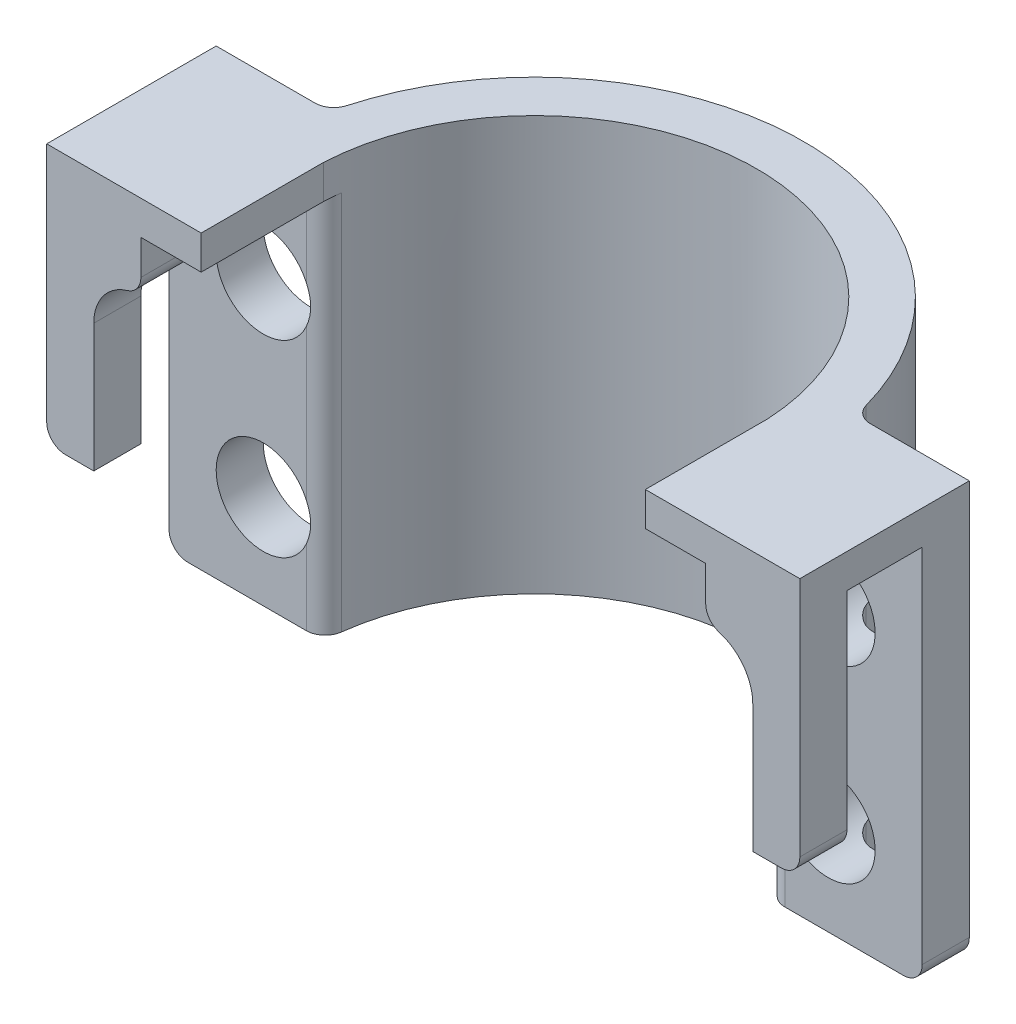
SolidWorks part; units mm, degrees
note: '?' marks a value the reader was unsure of.
ref_plane "Front Plane" through (0, 0, 0) normal (0, 0, 1) x (1, 0, 0)
ref_plane "Top Plane" through (0, 0, 0) normal (0, 1, 0) x (1, 0, 0)
ref_plane "Right Plane" through (0, 0, 0) normal (1, 0, 0) x (0, 0, -1)
sketch "Sketch2" plane through (0, 0, 0) normal (0, 1, 0) x (1, 0, 0)
  line L0 (0, 0) -> (-10.4194, 0)
  line L1 (-10.4194, 0) -> (-10.4194, 3.175)
  line L2 (-10.4194, 3.175) -> (-2.7628, 3.175)
  line L3 (32.7241, 3.175) -> (40.3806, 3.175)
  line L4 (40.3806, 3.175) -> (40.3806, 0)
  line L5 (40.3806, 0) -> (29.9613, 0)
  line L6 (14.9806, 0.1727) -> (14.9806, 50000.1727) construction
  circle A0 centre (14.9806, -0.762) radius 15 construction
  arc A1 (29.9613, 0) -> (0, 0) centre (14.9806, -0.762) ccw
  arc A2 (32.7241, 3.175) -> (-2.7628, 3.175) centre (14.9806, -0.762) ccw
  point P5 (-4.0694, 0)
  point P8 (34.0306, 0)
  dimension "D1" = 15
  dimension "D2" = 3.175
  dimension "D3" = 38.1
  dimension "D4" = 3.175
  dimension "D5" = 6.35
  dimension "D6" = 0.762
extrude "Boss-Extrude1" add sketch "Sketch2" against normal blind 27.94
sketch "Sketch3" plane through (0, 0, 0) normal (0, 0, 1) x (1, 0, 0)
  line L0 (14.9806, 0) -> (14.9806, -50000) construction
  line L1 (29.9613, 0) -> (0, 0) construction
  line L2 (-10.4194, 0) -> (0, 0) construction
  circle A0 centre (-4.0694, -8.89) radius 3.175
  circle A1 centre (34.0306, -8.89) radius 3.175
  circle A2 centre (-4.0694, -21.59) radius 3.175
  circle A3 centre (34.0306, -21.59) radius 3.175
  point P8 (14.9806, 0)
  dimension "D1" = 6.35
  dimension "D4" = 12.7
  dimension "D2" = 38.1
  dimension "D3" = 8.89
extrude "Cut-Extrude1" cut sketch "Sketch3" against normal through all
sketch "Sketch4" plane through (40.3806, 0, 0) normal (1, 0, 0) x (0, 0, -1)
  line L0 (-5.08, -17.526) -> (-8.255, -17.526)
  line L1 (-8.255, -17.526) -> (-8.255, 0)
  line L2 (-8.255, 0) -> (0, 0)
  line L3 (0, 0) -> (0, -2.286)
  line L4 (0, -27.94) -> (0, 0) construction
  line L5 (0, -2.286) -> (-5.08, -2.286)
  line L6 (-5.08, -2.286) -> (-5.08, -17.526)
  dimension "D1" = 2.286
  dimension "D2" = 3.175
  dimension "D3" = 5.08
  dimension "D4" = 15.24
extrude "Boss-Extrude2" add sketch "Sketch4" against normal up to vertex (10.7129 mm away)
sketch "Sketch5" plane through (0, 0, 8.255) normal (0, 0, 1) x (1, 0, 0)
  line L0 (29.9613, -17.526) -> (40.3806, -17.526) construction
  line L4 (37.2056, -8.89) -> (37.2056, -17.526)
  line L5 (29.9613, -2.286) -> (34.0306, -2.286)
  line L6 (29.9613, 0) -> (29.9613, -17.526) construction
  line L7 (34.0306, -2.286) -> (34.0306, -5.715)
  line L8 (29.9613, -2.286) -> (29.9613, -17.526)
  line L9 (29.9613, -27.94) -> (29.9613, -2.286) construction
  line L10 (29.9613, -17.526) -> (37.2056, -17.526)
  line L11 (29.9613, -2.286) -> (40.3806, -2.286) construction
  arc A2 (37.2056, -8.89) -> (34.0306, -5.715) centre (34.0306, -8.89) ccw
  circle A3 centre (34.0306, -8.89) radius 3.175 construction
extrude "Cut-Extrude2" cut sketch "Sketch5" against normal blind 6.35
ref_axis "Axis1" through (14.9806, -27.94, 0.762) along (0, 1, 0)?
ref_plane "Plane1" through (14.9806, 0, 0) normal (-1, 0, 0) x (0, 0, 1)
mirror "Mirror1" about plane through (14.9806, 0, 0) normal (-1, 0, 0) of "Boss-Extrude2", "Cut-Extrude2"
fillet "Fillet1" radius 1.27 14 edges at (32.7241, -2.9981, -3.175) (32.7241, -26.2119, -3.175) (32.7241, -15.24, -3.175) (-2.7628, -2.9981, -3.175) (-2.7628, -26.2119, -3.175) (-2.7628, -15.24, -3.175) (29.9613, -15.113, 0) (0, -15.113, 0) (-10.4194, -17.526, 6.6675) (-10.4194, -27.94, -1.5875) (40.3806, -27.94, -1.5875) (40.3806, -17.526, 6.6675) (34.0306, -5.715, 6.6675) (-4.0694, -5.715, 6.6675)
